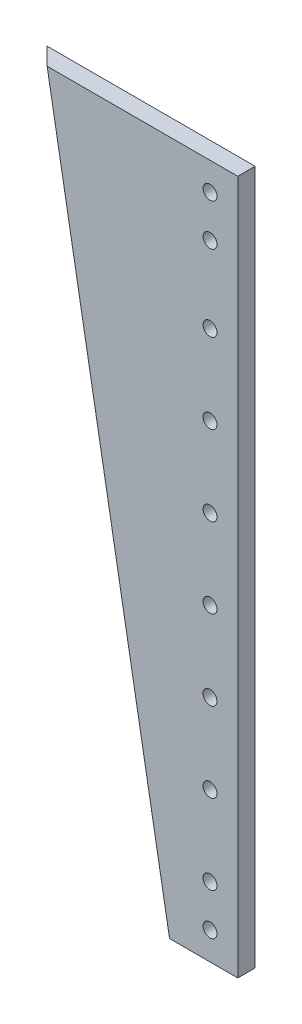
SolidWorks part; units mm, degrees
ref_plane "Front Plane" through (0, 0, 0) normal (0, 0, 1) x (1, 0, 0)
ref_plane "Top Plane" through (0, 0, 0) normal (0, 1, 0) x (1, 0, 0)
ref_plane "Right Plane" through (0, 0, 0) normal (1, 0, 0) x (0, 0, -1)
sketch "Sketch1" plane through (0, 0, 0) normal (0, 0, 1) x (1, 0, 0)
  line L1 (-60, 200) -> (0, 200)
  line L2 (-60, 200) -> (-60, 0)
  line L3 (-60, 0) -> (0, 0)
  line L4 (0, 200) -> (0, 0)
  dimension "D1" = 60
  dimension "D2" = 200
extrude "Boss-Extrude1" add sketch "Sketch1" along normal blind 5
sketch "Sketch3" plane through (-200, 0, 0) normal (0, 0, -1) x (-1, 0, 0)
  line L8 (-140, 0) -> (-175.2654, 0)
  line L9 (-140, 0) -> (-200, 0) construction
  line L10 (-140, 200) -> (-140, 0) construction
  line L11 (-175.2654, 0) -> (-140, 200)
  line L12 (-140, 200) -> (-140, 0)
  line L13 (-154.1062, 0) -> (-154.1062, 120) construction
  dimension "D1" = 10
  dimension "D2" = 120
extrude "Cut-Extrude2" cut sketch "Sketch3" against normal up to surface (5 mm away) up to face at (-30, 100, 5)
chamfer "Chamfer1" distance 5 angle 45 1 edges at (-42.3673, 100, 5)
sketch "Sketch6" plane through (0, 0, 0) normal (0, 0, 1) x (1, 0, 0)
  line L0 (-24.7346, 0) -> (0, 0) construction
  line L1 (0, 0) -> (0, 200) construction
  circle A0 centre (-8, 8) radius 2
  circle A1 centre (-8, 20) radius 2
  point P8 (0, 0)
  dimension "D1" = 4
  dimension "D2" = 8
  dimension "D3" = 12
  dimension "D4" = 8
extrude "Cut-Extrude3" cut sketch "Sketch6" along normal up to surface (5 mm away) up to face at (-18.6451, 100, 5)
ref_plane "Plane1" through (0, 100, 0) normal (0, 1, 0) x (1, 0, 0)
mirror "Mirror1" about plane through (0, 100, 0) normal (0, 1, 0) of "Cut-Extrude3"
sketch "Sketch7" plane through (0, 0, 0) normal (0, 0, 1) x (1, 0, 0)
  line L0 (-8, 43) -> (-8, 20) construction
  circle A0 centre (-8, 43) radius 2
  dimension "D2" = 4
  dimension "D1" = 23
extrude "Cut-Extrude4" cut sketch "Sketch7" along normal up to surface (5 mm away) up to face at (-6, 192, 5)
pattern_linear "LPattern1" count 6 spacing 23 along (0, 1, 0) of "Cut-Extrude4"
